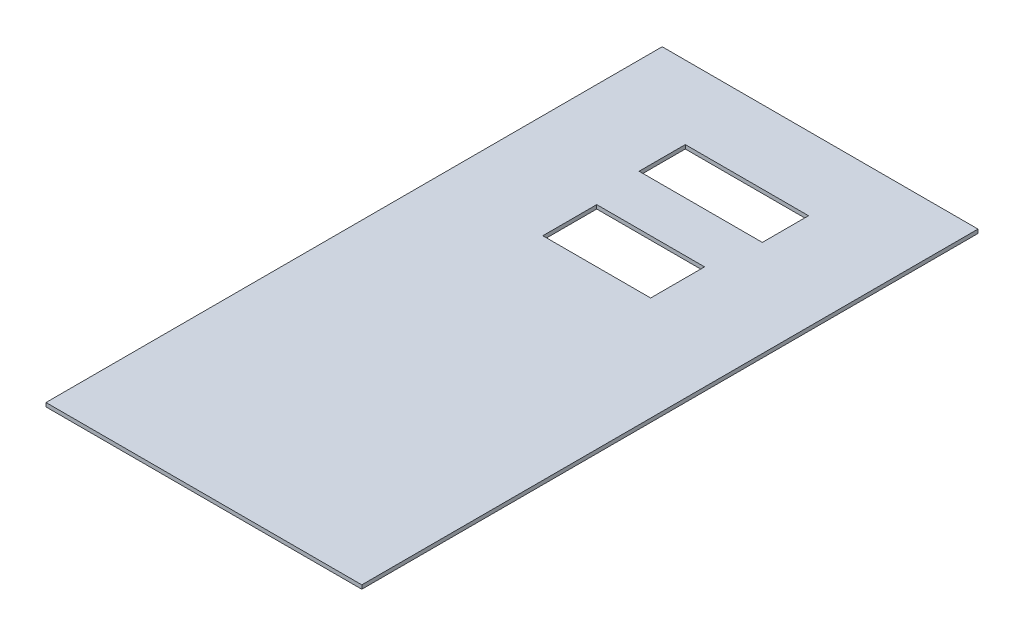
SolidWorks part; units mm, degrees
ref_plane "前视基准面" through (0, 0, 0) normal (0, 0, 1) x (1, 0, 0)
ref_plane "上视基准面" through (0, 0, 0) normal (0, 1, 0) x (1, 0, 0)
ref_plane "右视基准面" through (0, 0, 0) normal (1, 0, 0) x (0, 0, -1)
sketch "草图1" plane through (0, 0, 0) normal (0, 1, 0) x (1, 0, 0)
  line L0 (0, -55) -> (0, 55) construction
  line L1 (-41, 80) -> (41, 80)
  line L2 (41, 80) -> (41, -80)
  line L3 (-41, 80) -> (-41, -80)
  line L4 (-55, 0) -> (55, 0) construction
  line L5 (-41, -80) -> (41, -80)
  line L7 (0, 22) -> (14, 22)
  line L8 (14, 22) -> (14, 36)
  line L9 (14, 36) -> (-14, 36)
  line L10 (-14, 36) -> (-14, 22)
  line L11 (-14, 22) -> (0, 22)
  line L13 (-16, 61) -> (16, 61)
  line L15 (16, 61) -> (16, 49)
  line L17 (16, 49) -> (-16, 49)
  line L18 (-16, 61) -> (-16, 49)
  point P3 (0, -80)
  point P8 (0, 80)
  point P11 (-41, 0)
  point P12 (41, 0)
  point P26 (0, 49)
extrude "凸台-拉伸1" add sketch "草图1" along normal blind 1
